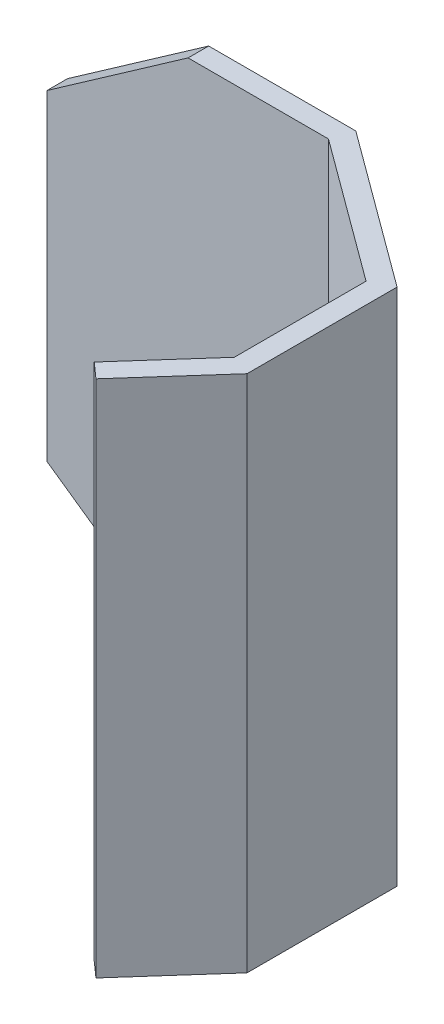
SolidWorks part; units mm, degrees
ref_plane "前视基准面" through (0, 0, 0) normal (0, 0, 1) x (1, 0, 0)
ref_plane "上视基准面" through (0, 0, 0) normal (0, 1, 0) x (1, 0, 0)
ref_plane "右视基准面" through (0, 0, 0) normal (1, 0, 0) x (0, 0, -1)
sketch "草图1" plane through (0, 0, 0) normal (0, 1, 0) x (1, 0, 0)
  line L0 (0, -8) -> (0, 8)
  line L1 (0, 8) -> (-17.2409, 20.6772)
  line L2 (0, -8) -> (-8, -17)
  line L3 (2.5, -8.9505) -> (-6.1315, -18.6609)
  line L4 (2.5, -8.9505) -> (2.5, 9.2648)
  line L5 (2.5, 9.2648) -> (-16.4207, 23.1772)
  line L6 (-6.1315, -18.6609) -> (-8, -17)
  line L7 (-17.2409, 20.6772) -> (-51.4207, 20.6772)
  line L8 (-51.4207, 23.1772) -> (-16.4207, 23.1772)
  line L9 (2.5, 9.2648) -> (-15.76, 22.6913) construction
  line L10 (-51.4207, 23.1772) -> (-51.4207, 20.6772)
  dimension "D1" = 16
  dimension "D2" = 21.4
  dimension "D3" = 126.327
  dimension "D4" = 9
  dimension "D5" = 8
  dimension "D7" = 2.5
  dimension "D8" = 35
  dimension "D6" = 2.5
extrude "凸台-拉伸1" add sketch "草图1" along normal blind 31.5 and the other way blind 31.5
chamfer "倒角1" distance 12 angle 55 2 edges at (-51.4207, -31.5, -21.9272) (-51.4207, 31.5, -21.9272) first distance on face at (-51.4207, 0, -21.9272)
